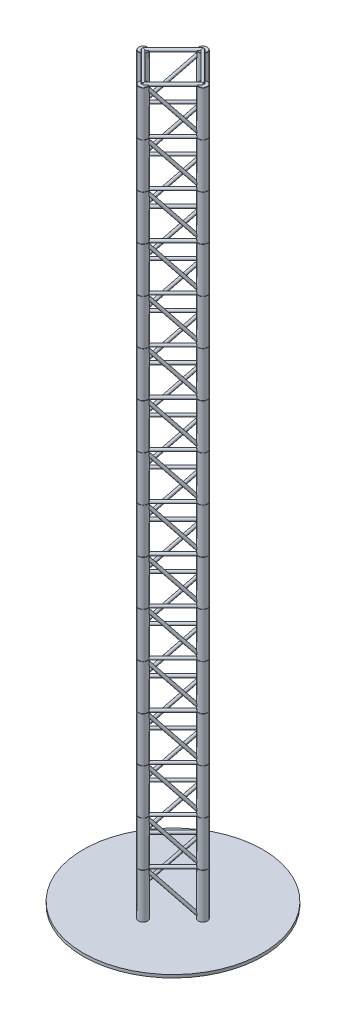
SolidWorks part; units mm, degrees
ref_plane "Front Plane" through (0, 0, 0) normal (0, 0, 1) x (1, 0, 0)
ref_plane "Top Plane" through (0, 0, 0) normal (0, 1, 0) x (1, 0, 0)
ref_plane "Right Plane" through (0, 0, 0) normal (1, 0, 0) x (0, 0, -1)
sketch "Sketch2" plane through (0, 0, 0) normal (0, 1, 0) x (1, 0, 0)
  circle A0 centre (0, 0) radius 76.2
extrude "Boss-Extrude1" add sketch "Sketch2" along normal blind 2.54
sketch "Sketch3" plane through (0, 2.54, 0) normal (0, 1, 0) x (1, 0, 0)
  line L0 (0, 0) -> (0, 25.4) construction
  line L1 (0, 0) -> (25.4, 0) construction
  line L2 (0, 0) -> (0, -25.4) construction
  line L3 (0, 0) -> (-25.4, 0) construction
  circle A0 centre (0, 25.4) radius 3.81
  circle A1 centre (25.4, 0) radius 3.81
  circle A2 centre (0, -25.4) radius 3.81
  circle A3 centre (-25.4, 0) radius 3.81
  point P13 (0, 0)
  dimension "D2" = 7.62
  dimension "D1" = 25.4
  dimension "D3" = 4
extrude "Boss-Extrude2" add sketch "Sketch3" along normal blind 38.1
sketch "Sketch4" plane through (0, 40.64, 0) normal (0, 1, 0) x (1, 0, 0)
  line L0 (0, 25.4) -> (0, 0) construction
  circle A1 centre (25.4, 0) radius 3.556
  circle A2 centre (0, 25.4) radius 3.556
  circle A3 centre (0, 25.4) radius 3.556
  circle A4 centre (0, -25.4) radius 3.556
  circle A5 centre (-25.4, 0) radius 3.556
  point P16 (0, 0)
  dimension "D1" = 0.254
  dimension "D2" = 4
extrude "Boss-Extrude3" add sketch "Sketch4" along normal blind 0.254
sketch "Sketch5" plane through (0, 2.54, 0) normal (0, 1, 0) x (1, 0, 0)
  line L0 (0, -25.4) -> (25.4, 0) construction
  line L1 (0, 0) -> (12.7, -12.7) construction
  circle A0 centre (25.4, 0) radius 3.81 construction
  circle A1 centre (25.4, 0) radius 3.81 construction
  circle A2 centre (0, -25.4) radius 3.81 construction
  circle A3 centre (0, -25.4) radius 3.81 construction
ref_plane "Plane1" through (12.7, 2.54, 12.7) normal (0.7071, 0, 0.7071) x (0.7071, 0, -0.7071)
sketch "Sketch7" plane through (12.7, 2.54, 12.7) normal (0.7071, 0, 0.7071) x (0.7071, 0, -0.7071)
  line L0 (21.7705, 38.1) -> (14.1505, 38.1) construction
  line L1 (-14.1505, 38.1) -> (-21.7705, 38.1) construction
  line L2 (-17.9605, 0) -> (17.9605, 0) construction
  line L3 (21.7705, 38.1) -> (14.1505, 38.1) construction
  line L4 (-14.1505, 38.1) -> (-21.7705, 38.1) construction
  line L5 (-17.9605, 0) -> (17.9605, 0) construction
  line L6 (-17.9605, 38.1) -> (17.9605, 0) construction
  line L7 (-17.9605, 38.1) -> (17.9605, 38.1) construction
  point P7 (0, 0)
  point P9 (0, 0)
ref_plane "Plane2" through (25.4, 2.54, 0) normal (-0.4851, 0.7276, 0.4851) x (0.8745, 0.4036, 0.2691)
ref_plane "Plane3" through (0, 40.64, 25.4) normal (0.7071, 0, -0.7071) x (-0.7071, 0, -0.7071)
sketch "Sketch9" plane through (25.4, 2.54, 0) normal (-0.4851, 0.7276, 0.4851) x (0.8745, 0.4036, 0.2691)
  circle A0 centre (0, 0) radius 1.27
  dimension "D1" = 2.54
extrude "Boss-Extrude4" add sketch "Sketch9" along normal up to vertex (52.3634 mm away) up to point (0, 40.64, 25.4)
sketch "Sketch10" plane through (0, 40.64, 25.4) normal (0.7071, 0, -0.7071) x (-0.7071, 0, -0.7071)
  circle A0 centre (0, 0) radius 1.27
  dimension "D1" = 2.54
extrude "Boss-Extrude5" add sketch "Sketch10" along normal up to vertex (35.921 mm away) up to point (25.4, 40.64, 0)
pattern_circular "CirPattern1" count 4 over 360 about axis through (0, 2.54, 0) along (0, -1, 0) of "Boss-Extrude5", "Boss-Extrude4" reverse direction yes
ref_axis "Axis1" through (0, 2.54, 0) along (0, -1, 0)
pattern_linear "LPattern1" count 2 spacing 38.354 along (0, 1, 0) of "Boss-Extrude2", "Boss-Extrude3", "Boss-Extrude4", "Boss-Extrude5", "CirPattern1"
pattern_linear "LPattern2" count 15 spacing 38.354 along (0, 1, 0) of "LPattern1"
